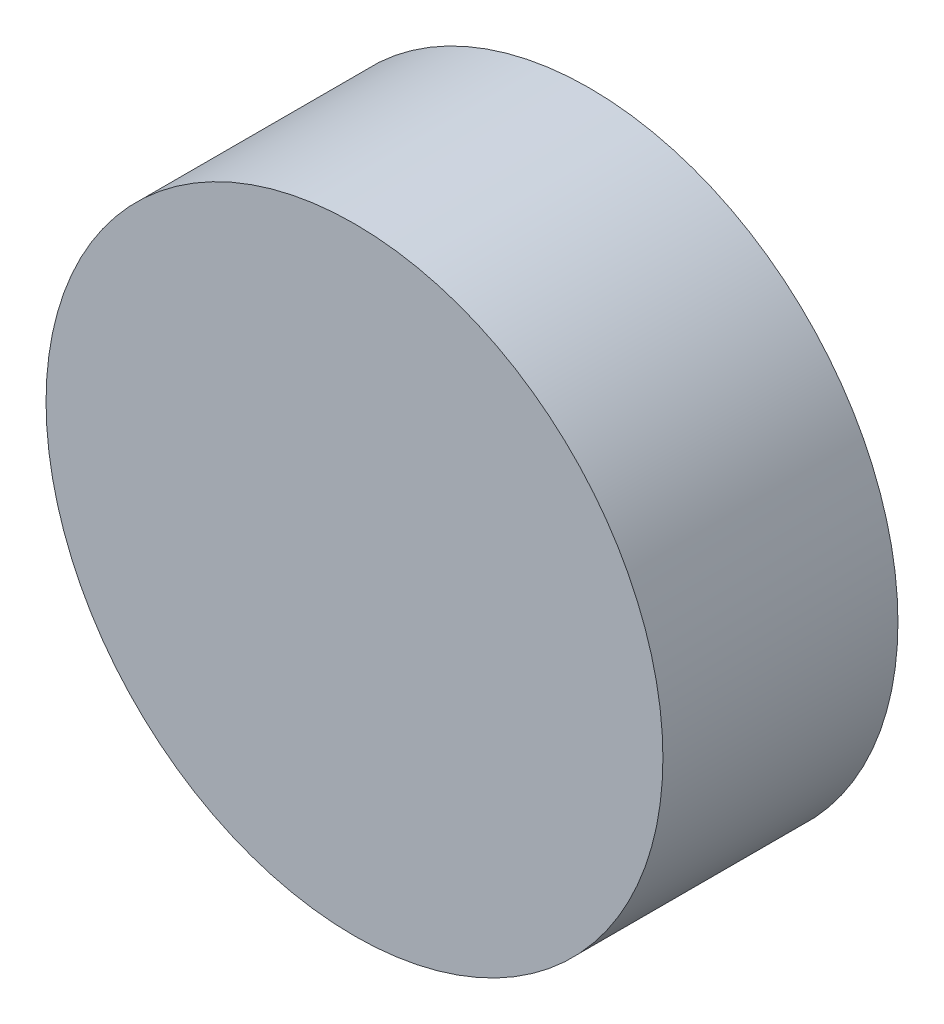
SolidWorks part; units mm, degrees
material "6061-T6 (SS)"
ref_plane "Front Plane" through (0, 0, 0) normal (0, 0, 1) x (1, 0, 0)
ref_plane "Top Plane" through (0, 0, 0) normal (0, 1, 0) x (1, 0, 0)
ref_plane "Right Plane" through (0, 0, 0) normal (1, 0, 0) x (0, 0, -1)
sketch "Sketch1" plane through (0, 0, 0) normal (0, 0, 1) x (1, 0, 0)
  circle A0 centre (0, 0) radius 25
  dimension "D1" = 50
extrude "Boss-Extrude1" add sketch "Sketch1" along normal mid plane 19.05
